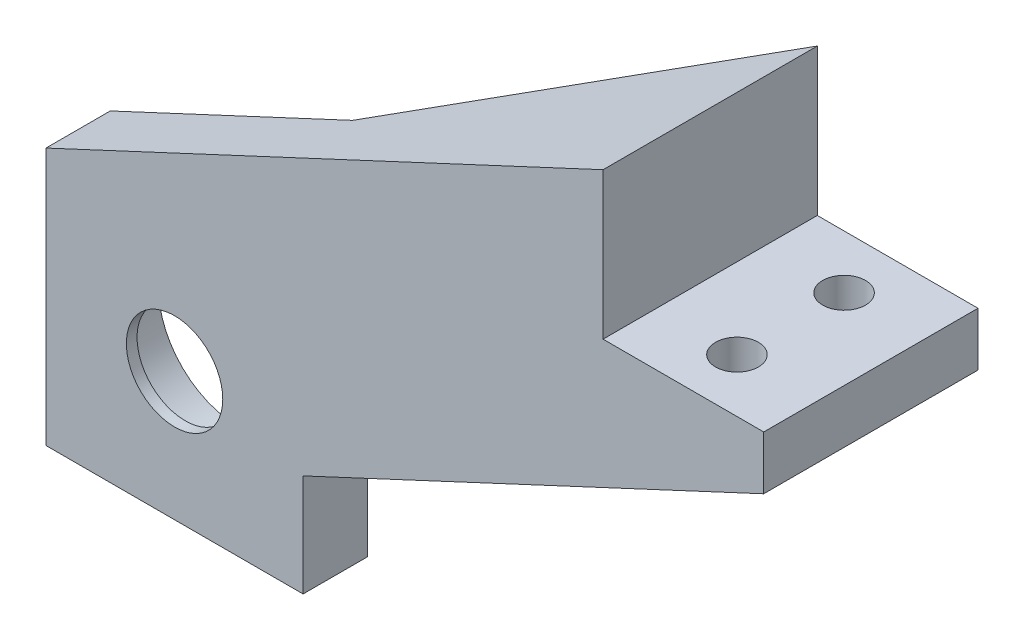
SolidWorks part; units mm, degrees
material "ABS"
ref_plane "Front Plane" through (0, 0, 0) normal (0, 0, 1) x (1, 0, 0)
ref_plane "Top Plane" through (0, 0, 0) normal (0, 1, 0) x (1, 0, 0)
ref_plane "Right Plane" through (0, 0, 0) normal (1, 0, 0) x (0, 0, -1)
sketch "Sketch1" plane through (0, 0, 0) normal (0, 0, 1) x (1, 0, 0)
  circle A0 centre (0, 0) radius 7.5
  circle A1 centre (0, 0) radius 4.5
  circle A2 centre (0, 0) radius 10
  dimension "D1" = 15
  dimension "D2" = 20
  dimension "D3" = 9
extrude "Boss-Extrude1" add sketch "Sketch1" against normal up to surface (5 mm away) contours A2 A0 region at (-9.7172, 0, 0)
extrude "Boss-Extrude2" add sketch "Sketch1<3>" along normal blind 1 contours A0 A1 | A2 A0 region at (-7.2879, 0, 0) region at (-9.7172, 0, 0)
sketch "Sketch1<3>" plane through (0, 0, 0) normal (0, 0, 1) x (1, 0, 0) same geometry as "Sketch1"
sketch "Sketch2" plane through (0, 0, 1) normal (0, 0, 1) x (1, 0, 0)
  line L3 (55, 22.6) -> (40, 22.6)
  line L5 (-12, -0.9326) -> (-12, -12)
  line L6 (-12, -12) -> (12, -12)
  line L8 (40, 22.6) -> (40, 17.6)
  line L13 (40, 17.6) -> (55, 17.6)
  line L14 (55, 17.6) -> (55, 22.6)
  line L15 (-86, 22.6) -> (266, 22.6) construction
  line L16 (10.6203, 22.6) -> (-12, 12.052)
  line L17 (-12, -0.9326) -> (-12, 12.052)
  line L18 (40, 22.6) -> (10.6203, 22.6)
  line L19 (55, 17.6) -> (12, -2.4512)
  line L20 (12, -2.4512) -> (12, -12)
  line L21 (10.6203, 22.6) -> (40, 36.3)
  line L23 (34.0705, 37.9485) -> (-8.8692, 17.9254) construction
  line L24 (40, 22.6) -> (40, 34.3) construction
  line L25 (40, 36.3) -> (40, 22.6)
  circle A1 centre (0, 0) radius 10
  circle A2 centre (0, 0) radius 10 construction
  circle M4 centre (0, 0) radius 10
  dimension "D1" = 12
  dimension "D2" = 24
  dimension "D3" = 15
  dimension "D4" = 5
  dimension "D5" = 25
  dimension "D6" = 4
  dimension "D7" = 12
  dimension "D8" = 2
  dimension "D9" = 0
extrude "Boss-Extrude3" add sketch "Sketch2" against normal up to surface (6 mm away) contours L8 M4 | L6 L5 M4 | L8 | L25 L21 L18 region at (47.5, 20.1, 1) region at (16.0369, 9.9628, 1) region at (30.2068, 27.1667, 1) up to face at (-10, 0, -5)
sketch "Sketch3" plane through (0, 22.6, 0) normal (0, -1, 0) x (1, 0, 0)
  line L0 (40, -286) -> (40, 14) construction
  line L1 (55, -5) -> (40, -5)
  line L2 (55, -5) -> (55, -19)
  line L3 (55, -19) -> (40, -19)
  line L4 (40, -5) -> (40, -19)
  line L5 (55, -5) -> (40, -19) construction
  line L6 (55, -19) -> (40, -5) construction
  line L7 (55, 1) -> (12, 1) construction
  line L8 (40, -19) -> (10.6203, -5)
  line L9 (55, -5) -> (55, 1) construction
  line L10 (40, -5) -> (10.6203, -5)
  line L11 (40, -5) -> (-12, -5) construction
  point P4 (47.5, -12)
  dimension "D1" = 20
  dimension "D2" = 29.3797
extrude "Boss-Extrude7" add sketch "Sketch3" along normal up to surface (11.9946 mm away) contours L4 L10 L8 | L1 L4 L3 L2 region at (47.5, 22.6, -12) region at (30.2068, 22.6, -9.6667) up to face at (33.5, 7.5744, -2)
sketch "Sketch4" plane through (0, 22.6, 0) normal (0, -1, 0) x (1, 0, 0)
  line L1 (55, 1) -> (40, 1)
  line L2 (55, 1) -> (55, -19)
  line L3 (55, -19) -> (40, -19)
  line L4 (40, 1) -> (40, -19)
  line L5 (55, 1) -> (40, -19) construction
  line L6 (55, -19) -> (40, 1) construction
  line L7 (55, -19) -> (55, 1) construction
  line L8 (55, -9) -> (40, -9) construction
  line L9 (47.5, -9.9585) -> (44, -11.9793)
  line L10 (44, -11.9793) -> (44, -16.0207)
  line L11 (44, -16.0207) -> (47.5, -18.0415)
  line L12 (47.5, -18.0415) -> (51, -16.0207)
  line L13 (51, -16.0207) -> (51, -11.9793)
  line L14 (51, -11.9793) -> (47.5, -9.9585)
  line L21 (51, -6.0207) -> (47.5, -8.0415)
  line L22 (51, -1.9793) -> (51, -6.0207)
  line L23 (47.5, 0.0415) -> (51, -1.9793)
  line L24 (44, -1.9793) -> (47.5, 0.0415)
  line L25 (44, -6.0207) -> (44, -1.9793)
  line L26 (47.5, -8.0415) -> (44, -6.0207)
  line L27 (55, 1) -> (40, 1) construction
  circle A0 centre (47.5, -14) radius 3.5 construction
  circle A1 centre (47.5, -4) radius 3.5 construction
  circle A2 centre (47.5, -14) radius 2
  circle A3 centre (47.5, -4) radius 2
  point P4 (47.5, -9)
  point P28 (45.75, -10.9689)
  dimension "D3" = 4
  dimension "D1" = 7.5
  dimension "D2" = 7
  dimension "D4" = 5
  dimension "D5" = 15
  dimension "D6" = 20
extrude "Cut-Extrude4" cut sketch "Sketch4" along normal through all contours A2 | A3 region at (47.5, 22.6, -14) region at (47.5, 22.6, -4)
extrude "Cut-Extrude5" cut sketch "Sketch4<3>" along normal through all from offset 3 contours L26 L21 L22 L23 L24 L25 A3 | L13 L14 L9 L10 L11 L12 A2 region at (49.1965, 22.6, -11.0615) region at (49.1965, 22.6, -6.9385)
sketch "Sketch4<3>" plane through (0, 22.6, 0) normal (0, -1, 0) x (1, 0, 0) same geometry as "Sketch4"
extrude "Boss-Extrude8" add sketch "Sketch3<4>" against normal up to surface (13.7 mm away) contours L4 L10 L8 region at (30.2068, 22.6, -9.6667) up to face at (13.3241, 23.8608, -2.6)
sketch "Sketch3<4>" plane through (0, 22.6, 0) normal (0, -1, 0) x (1, 0, 0) same geometry as "Sketch3"
